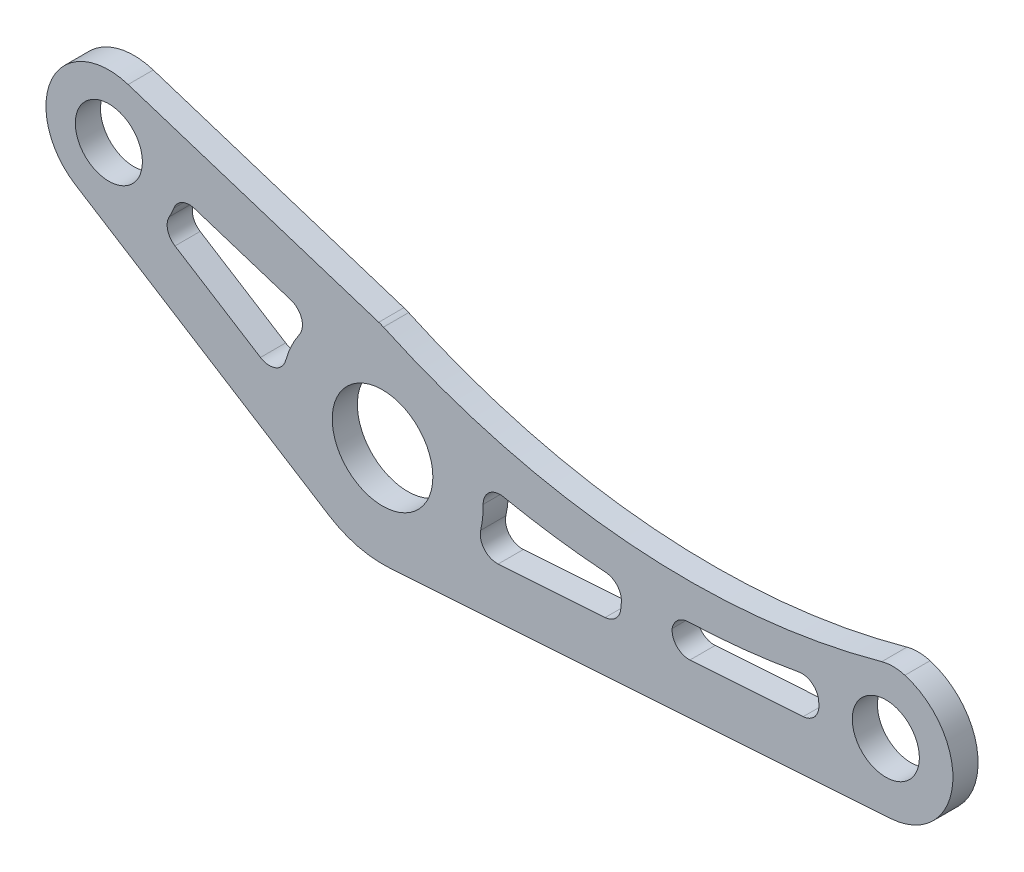
SolidWorks part; units mm, degrees
material "6061 合金"
ref_plane "前视基准面" through (0, 0, 0) normal (0, 0, 1) x (1, 0, 0)
ref_plane "上视基准面" through (0, 0, 0) normal (0, 1, 0) x (1, 0, 0)
ref_plane "右视基准面" through (0, 0, 0) normal (1, 0, 0) x (0, 0, -1)
other "Configuration Table"
sketch "草图1" plane through (0, 0, 0) normal (0, 0, 1) x (1, 0, 0)
  line L0 (0, 0) -> (60, 0)
  line L1 (0, 0) -> (-32.6271, 15.2143)
  line L2 (60.5333, -7.9822) -> (0.8, -11.9733)
  line L3 (4.7194, 11.7114) -> (60.5333, 7.9822)
  line L4 (-36.6215, 8.8665) -> (-6.3911, -10.1565)
  line L5 (-30.332, 22.3545) -> (-0.0675, 12.6264)
  arc A0 (-6.3911, -10.1565) -> (0.8, -11.9733) centre (0, 0) ccw
  arc A1 (-30.332, 22.3545) -> (-36.6215, 8.8665) centre (-32.6271, 15.2143) ccw
  arc A2 (60.5333, -7.9822) -> (60.5333, 7.9822) centre (60, 0) ccw
  arc A4 (4.7194, 11.7114) -> (-0.0675, 12.6264) centre (6.0528, 31.6669) cw
  dimension "D4" = 16
  dimension "D5" = 15
  dimension "D6" = 24
  dimension "D7" = 20
  dimension "D1" = 60
  dimension "D2" = 36
  dimension "D3" = 155
extrude "凸台-拉伸1" add sketch "草图1" along normal blind 3 contours L3 A4 L5 A1 L4 A0 L2 A2 region at (12.4558, 2.833, 0)
sketch "草图2" plane through (0, 0, 3) normal (0, 0, 1) x (1, 0, 0)
  circle A0 centre (-32.6271, 15.2143) radius 4
  circle A1 centre (60, 0) radius 4
  circle A2 centre (0, 0) radius 6
  dimension "D1" = 8
  dimension "D2" = 8
  dimension "D3" = 12
extrude "切除-拉伸1" cut sketch "草图2" against normal blind 5
sketch "草图3" plane through (0, 0, 3) normal (0, 0, 1) x (1, 0, 0)
  line L4 (32.6264, 9.8468) -> (30.6667, -9.9778)
  line L5 (4.7194, 11.7114) -> (60.5333, 7.9822) construction
  line L6 (60.5333, -7.9822) -> (0.8, -11.9733) construction
  line L7 (29.6409, 10.1419) -> (27.6812, -9.6826)
  line L8 (60.1333, 1.9956) -> (4.3194, 5.7248)
  line L9 (-1.9036, 6.9142) -> (-32.1681, 16.6423)
  line L10 (-33.426, 13.9447) -> (-3.1956, -5.0782)
  line L11 (0.4, -5.9867) -> (60.1333, -1.9956)
  line L12 (60.1333, 1.9956) -> (4.3194, 5.7248)
  line L13 (-1.9036, 6.9142) -> (-32.1681, 16.6423)
  line L14 (-33.426, 13.9447) -> (-3.1956, -5.0782)
  line L15 (0.4, -5.9867) -> (60.1333, -1.9956)
  line L16 (35.6118, 9.5517) -> (33.6521, -10.2729)
  circle A4 centre (0, 0) radius 12
  circle A5 centre (-32.6271, 15.2143) radius 8.2703
  circle A6 centre (60, 0) radius 8
  arc A8 (-1.9036, 6.9142) -> (4.3194, 5.7248) centre (6.0528, 31.6669) ccw
  arc A9 (-32.1681, 16.6423) -> (-33.426, 13.9447) centre (-32.6271, 15.2143) ccw
  arc A10 (-3.1956, -5.0782) -> (0.4, -5.9867) centre (0, 0) ccw
  arc A11 (60.1333, -1.9956) -> (60.1333, 1.9956) centre (60, 0) ccw
  arc A12 (-1.9036, 6.9142) -> (4.3194, 5.7248) centre (6.0528, 31.6669) ccw
  arc A13 (-32.1681, 16.6423) -> (-33.426, 13.9447) centre (-32.6271, 15.2143) ccw
  arc A14 (-3.1956, -5.0782) -> (0.4, -5.9867) centre (0, 0) ccw
  arc A15 (60.1333, -1.9956) -> (60.1333, 1.9956) centre (60, 0) ccw
  dimension "D1" = 6
  dimension "D2" = 3
  dimension "D3" = 3
extrude "切除-拉伸2" cut sketch "草图3" against normal blind 10 contours A4 L15 L7 L12 | A5 L14 A4 L13 | A6 L12 L16 L15 region at (42.8536, -0.0306, 3) region at (19.771, 0.0286, 3) region at (-17.2239, 8.0316, 3)
fillet "圆角1" radius 2 12 edges at (52.4046, -2.5119, 1.5) (34.2997, -3.7216, 1.5) (35.0307, 3.6728, 1.5) (52.4046, 2.5119, 1.5) (10.7692, 5.2938, 1.5) (29.041, 4.073, 1.5) (28.2304, -4.1272, 1.5) (10.7692, -5.2938, 1.5) (-24.4251, 14.1534, 1.5) (-8.0577, 8.8924, 1.5) (-11.9913, 0.4566, 1.5) (-26.5423, 9.6131, 1.5)
sketch "草图4" plane through (0, 0, 3) normal (0, 0, 1) x (1, 0, 0)
  circle A0 centre (36.4039, 91.051) radius 86.5023
  circle A1 centre (36.4039, 91.051) radius 98.0588 construction
  circle A2 centre (60, 0) radius 4 construction
sketch "草图5" plane through (0, 0, 3) normal (0, 0, 1) x (1, 0, 0)
  line L0 (-30.332, 22.3545) -> (-0.0675, 12.6264) construction
  line L1 (-24.5404, 20.4928) -> (-0.0675, 12.6264)
  arc A0 (-24.5404, 20.4928) -> (65.3351, 5.9612) centre (33.25, 92.7183) ccw
  circle A2 centre (0, 0) radius 6 construction
  circle A3 centre (60, 0) radius 4 construction
  arc A4 (-0.0675, 12.6264) -> (59.9446, 7.9998) centre (36.0489, 89.5718) ccw
  arc A6 (65.3351, 5.9612) -> (59.9446, 7.9998) centre (60, 0) ccw
  dimension "D1" = 185
  dimension "D2" = 8
  dimension "D3" = 85
extrude "凸台-拉伸2" add sketch "草图5" against normal blind 3
fillet "圆角3" radius 2 4 edges at (51.4827, 2.0331, 1.5) (34.6903, 0.2295, 1.5) (28.6712, 0.3317, 1.5) (11.6804, 2.7683, 1.5)
sketch "草图6" plane through (0, 0, 0) normal (0, 0, -1) x (-1, 0, 0)
  circle A0 centre (-60, 0) radius 8
  dimension "D1" = 16
extrude "凸台-拉伸3" add sketch "草图6" along normal blind 0.25
sketch "草图7" plane through (0, 0, -0.25) normal (0, 0, -1) x (-1, 0, 0)
  circle A0 centre (-60, 0) radius 6 construction
  circle A1 centre (-60, 0) radius 7
  circle A2 centre (-60, 0) radius 5
  dimension "D1" = 12
  dimension "D2" = 1
  dimension "D3" = 1
extrude "切除-拉伸4" cut sketch "草图7" against normal blind 1
extrude "切除-拉伸5" cut sketch "草图4" against normal blind 11
fillet "圆角5" radius 5 2 edges at (-0.1589, 12.6558, 1.5) (60.5333, 7.9822, 1.375)
fillet "圆角6" radius 1 2 edges at (55, 0, 0.75) (53, 0, 0.75)
sketch "草图8" plane through (0, 0, -0.25) normal (0, 0, -1) x (-1, 0, 0)
  circle A0 centre (-60, 0) radius 14.0704
extrude "切除-拉伸6" cut sketch "草图8" against normal blind 0.25
